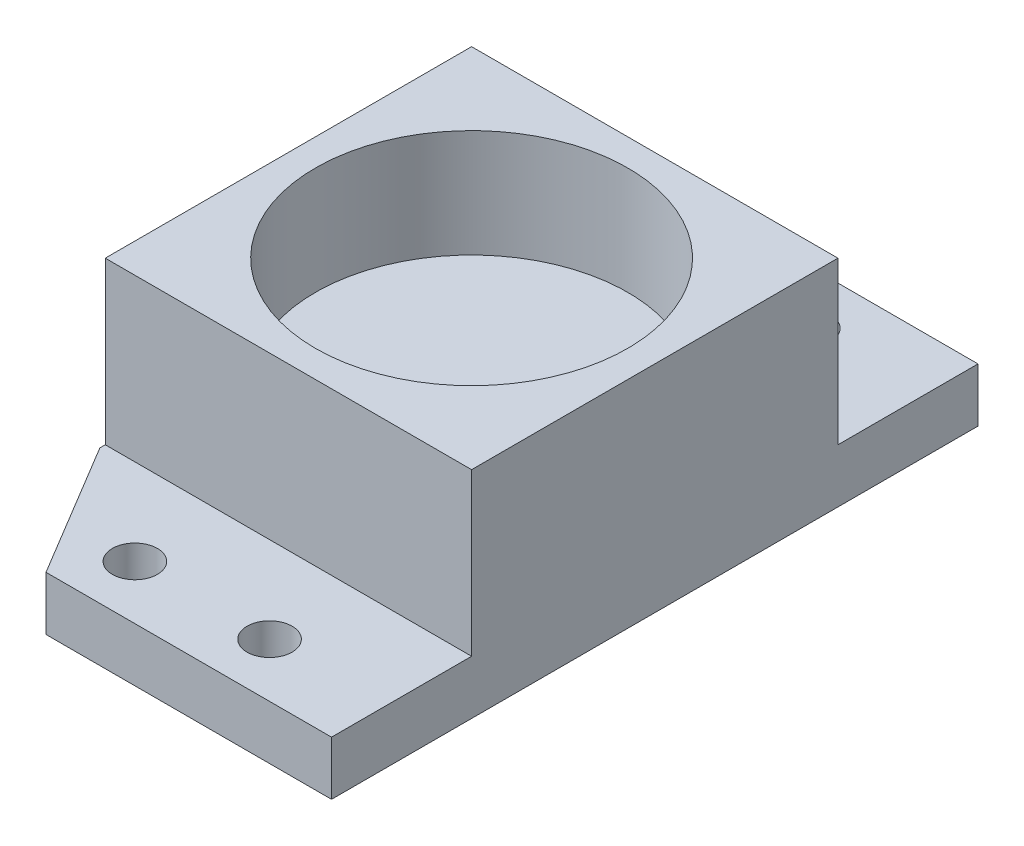
SolidWorks part; units mm, degrees
ref_plane "Front Plane" through (0, 0, 0) normal (0, 0, 1) x (1, 0, 0)
ref_plane "Top Plane" through (0, 0, 0) normal (0, 1, 0) x (1, 0, 0)
ref_plane "Right Plane" through (0, 0, 0) normal (1, 0, 0) x (0, 0, -1)
sketch "Sketch2" plane through (0, 0, 0) normal (0, 1, 0) x (1, 0, 0)
  line L1 (-38.1, -38.1) -> (38.1, -38.1)
  line L2 (-38.1, -38.1) -> (-38.1, 38.1)
  line L3 (-38.1, 38.1) -> (38.1, 38.1)
  line L4 (38.1, -38.1) -> (38.1, 38.1)
  line L5 (-38.1, -38.1) -> (38.1, 38.1) construction
  line L6 (-38.1, 38.1) -> (38.1, -38.1) construction
  circle A1 centre (0, 0) radius 38.1
  dimension "D1" = 76.2
extrude "Boss-Extrude1" add sketch "Sketch2" along normal blind 25.4 contours A1 L3 L2 | A1 | A1 L4 L3 | A1 L1 L4 | A1 L2 L1 region at (-29.5897, 0, 29.5897) region at (29.5897, 0, 29.5897) region at (0, 0, 0) region at (-29.5897, 0, -29.5897) region at (29.5897, 0, -29.5897)
sketch "Sketch3" plane through (0, 25.4, 0) normal (0, 1, 0) x (1, 0, 0)
  line L0 (-38.1, 38.1) -> (38.1, 38.1) construction
  line L2 (-21.59, -21.59) -> (21.59, -21.59)
  line L3 (-21.59, -21.59) -> (-21.59, 21.59)
  line L4 (-21.59, 21.59) -> (21.59, 21.59)
  line L5 (21.59, -21.59) -> (21.59, 21.59)
  line L6 (-21.59, -21.59) -> (21.59, 21.59) construction
  line L7 (-21.59, 21.59) -> (21.59, -21.59) construction
  circle A0 centre (0, 0) radius 18.415
  circle A1 centre (0, 0) radius 21.59
  circle A4 centre (0, 0) radius 38.1
  line M9 (-38.1, 38.1) -> (-38.1, -38.1)
  line M10 (-38.1, -38.1) -> (38.1, -38.1)
  line M11 (38.1, -38.1) -> (38.1, 38.1)
  line M12 (38.1, 38.1) -> (-38.1, 38.1)
  dimension "D1" = 36.83
  dimension "D2" = 3.175
extrude "Cut-Extrude1" cut sketch "Sketch3" against normal blind 12.7 contours A0
extrude "Cut-Extrude2" cut sketch "Sketch3<4>" against normal blind 19.05 contours A4 L5 L2 L3 L4 | A4 M9 M10 | A4 M12 M9 | A4 M11 M12 | A4 M10 M11 region at (26.1788, 25.4, 26.1788) region at (29.5897, 25.4, 29.5897) region at (29.5897, 25.4, -29.5897) region at (-29.5897, 25.4, -29.5897) region at (-29.5897, 25.4, 29.5897)
sketch "Sketch3<4>" plane through (0, 25.4, 0) normal (0, 1, 0) x (1, 0, 0) same geometry as "Sketch3"
sketch "Sketch5" plane through (0, 6.35, 0) normal (0, 1, 0) x (1, 0, 0)
  line L0 (38.1, 38.1) -> (-38.1, 38.1) construction
  line L5 (-21.59, -38.1) -> (21.59, -38.1)
  line L6 (-21.59, -38.1) -> (-21.59, 38.1)
  line L11 (-21.59, 38.1) -> (21.59, 38.1)
  line L12 (21.59, -38.1) -> (21.59, 38.1)
  line L13 (-21.59, -38.1) -> (21.59, 38.1) construction
  line L14 (-21.59, 38.1) -> (21.59, -38.1) construction
  line L15 (-21.59, -21.59) -> (-21.59, 21.59) construction
  line L16 (38.1, -38.1) -> (38.1, 38.1) construction
  line L17 (-38.1, -38.1) -> (38.1, -38.1) construction
  line L18 (-38.1, 38.1) -> (-38.1, -38.1) construction
  line L19 (38.1, -38.1) -> (38.1, 38.1)
  line L20 (-38.1, -38.1) -> (38.1, -38.1)
  line L21 (-38.1, 38.1) -> (-38.1, -38.1)
  line L22 (38.1, 38.1) -> (-38.1, 38.1)
  point P0 (0, 0)
extrude "Cut-Extrude3" cut sketch "Sketch5" against normal blind 12.7 contours L6 L22 L21 L20 | L19 L22 L12 L20 region at (-29.845, 6.35, 0) region at (29.845, 6.35, 0)
sketch "Sketch6" plane through (0, 6.35, 0) normal (0, 1, 0) x (1, 0, 0)
  line L0 (-18.415, 0) -> (21.59, 0) construction
  line L1 (0, 21.59) -> (0, -18.415) construction
  line L2 (-21.59, 21.59) -> (21.59, 21.59) construction
  line L3 (21.59, -21.59) -> (21.59, 21.59) construction
  circle A0 centre (0, 0) radius 18.415 construction
  point P7 (-7.9375, -31.75)
  point P8 (7.9375, -31.75)
  point P9 (-7.9375, 31.75)
  point P10 (7.9375, 31.75)
  dimension "D1" = 15.875
  dimension "D2" = 31.75
hole_wizard "#4 (0.209) Diameter Hole1" positions "Sketch7" profile "Sketch8" hole size "#4" standard "ANSI Inch" end condition up to next
sketch "Sketch7" plane through (0, 6.35, 0) normal (0, 1, 0) x (1, 0, 0)
  point P0 (7.9375, 31.75)
  point P3 (-7.9375, 31.75)
  point P6 (7.9375, -31.75)
  point P9 (-7.9375, -31.75)
sketch "Sketch8" plane through (7.9375, 6.35, -31.75) normal (1, 0, 0) x (0, 0, 1)
  line L0 (0, 0) -> (0, 6.35)
  line L1 (0, 6.35) -> (2.6543, 6.35)
  line L2 (2.6543, 6.35) -> (2.6543, 0)
  line L5 (2.6543, 0) -> (0, 0)
  line L11 (0, -6.35) -> (0, 107.95) construction
  dimension "Thru Hole Dia." = 5.3086
  dimension "Thru Hole Depth" = 6.35
chamfer "Chamfer1" distance 15.875 distance2 9.525 1 edges at (-21.59, 3.175, -38.1) first distance on face at (-21.59, 9.525, 0)
chamfer "Chamfer2" distance 9.525 distance2 15.875 1 edges at (-21.59, 3.175, 38.1) first distance on face at (0, 3.175, 38.1)
